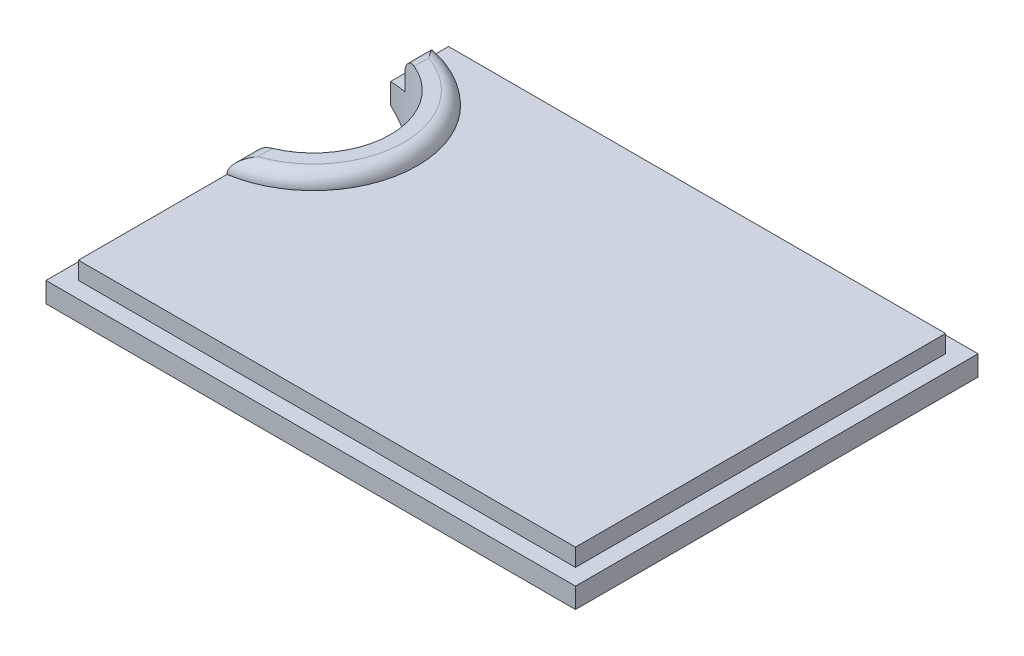
SolidWorks part; units mm, degrees
ref_plane "Front Plane" through (0, 0, 0) normal (0, 0, 1) x (1, 0, 0)
ref_plane "Top Plane" through (0, 0, 0) normal (0, 1, 0) x (1, 0, 0)
ref_plane "Right Plane" through (0, 0, 0) normal (1, 0, 0) x (0, 0, -1)
sketch "Sketch1" plane through (0, 0, 0) normal (0, 1, 0) x (1, 0, 0)
  line L0 (-19.6, 14.9) -> (-19.6, -14.9)
  line L1 (-19.6, -14.9) -> (19.6, -14.9)
  line L2 (19.6, -14.9) -> (19.6, 14.9)
  line L3 (19.6, 14.9) -> (-19.6, 14.9)
  line L4 (18.4, 13.7) -> (-18.4, 13.7)
  line L5 (-18.4, 13.7) -> (-18.4, -13.7)
  line L6 (-18.4, -13.7) -> (18.4, -13.7)
  line L7 (18.4, -13.7) -> (18.4, 13.7)
  line L8 (-18.4, 13.7) -> (0, 0) construction
  line L9 (0, 0) -> (18.4, -13.7) construction
  line L10 (0, 0) -> (18.4, 13.7) construction
  line L11 (0, 0) -> (-18.4, -13.7) construction
  arc A0 (-19.6, 10.6) -> (-19.6, -0.8) centre (-19.6, 4.9) cw
  arc A1 (-19.6, 12.6) -> (-19.6, -2.8) centre (-19.6, 4.9) cw
  dimension "D4" = 5.7
  dimension "D6" = 2
  dimension "D1" = 29.8
  dimension "D2" = 39.2
  dimension "D5" = 10
  dimension "D3" = 1.2
extrude "Boss-Extrude1" add sketch "Sketch1" along normal blind 1 contours L5 A1 L6 L7 L4 | A1 L5 A0 | L0 A1 L5 L4 L7 L6 L1 L2 L3 | A1 L5 A0 L0 | A1 L0 A0 L5 region at (0, 0, -14.4076) region at (-18.9983, 0, -11.563) region at (-12.0654, 0, -4.9) region at (1.2546, 0, 0.3922) region at (-18.9983, 0, 1.763)
extrude "Boss-Extrude2" add sketch "Sketch1<5>" along normal blind 1.6 from surface contours L5 A1 L6 L7 L4 | A1 L5 A0 | A1 L0 A0 L5 | L0 A1 L5 L4 L7 L6 L1 L2 L3 | A1 L5 A0 L0 region at (0, 0, -14.4076) region at (-18.9983, 0, -11.563) region at (-12.0654, 0, -4.9) region at (1.2546, 0, 0.3922) region at (-18.9983, 0, 1.763) starting at face at (-5.5833, 1, -1.6333)
sketch "Sketch1<5>" plane through (0, 0, 0) normal (0, 1, 0) x (1, 0, 0) same geometry as "Sketch1"
extrude "Boss-Extrude3" add sketch "Sketch1<6>" along normal blind 1.3 from surface contours L5 A1 L6 L7 L4 | A1 L5 A0 region at (-12.0654, 0, -4.9) region at (1.2546, 0, 0.3922) starting at face at (-5.5833, 2.6, -1.6333)
sketch "Sketch1<6>" plane through (0, 0, 0) normal (0, 1, 0) x (1, 0, 0) same geometry as "Sketch1"
extrude "Boss-Extrude4" add sketch "Sketch1<8>" along normal blind 1 from surface contours A1 L5 A0 region at (-12.0654, 0, -4.9) starting at face at (-5.3833, 3.9, -1.6333)
sketch "Sketch1<8>" plane through (0, 0, 0) normal (0, 1, 0) x (1, 0, 0) same geometry as "Sketch1"
fillet "Fillet1" radius 1 3 edges at (-11.9, 4.9, -4.9) (-18.4, 4.9, 1.6891) (-18.4, 4.9, -11.4891)
chamfer "Chamfer1" distance 1.1 angle 45 5 edges at (-19.6, 0, -12.75) (0, 0, -14.9) (19.6, 0, 0) (0, 0, 14.9) (-19.6, 0, 7.85)
